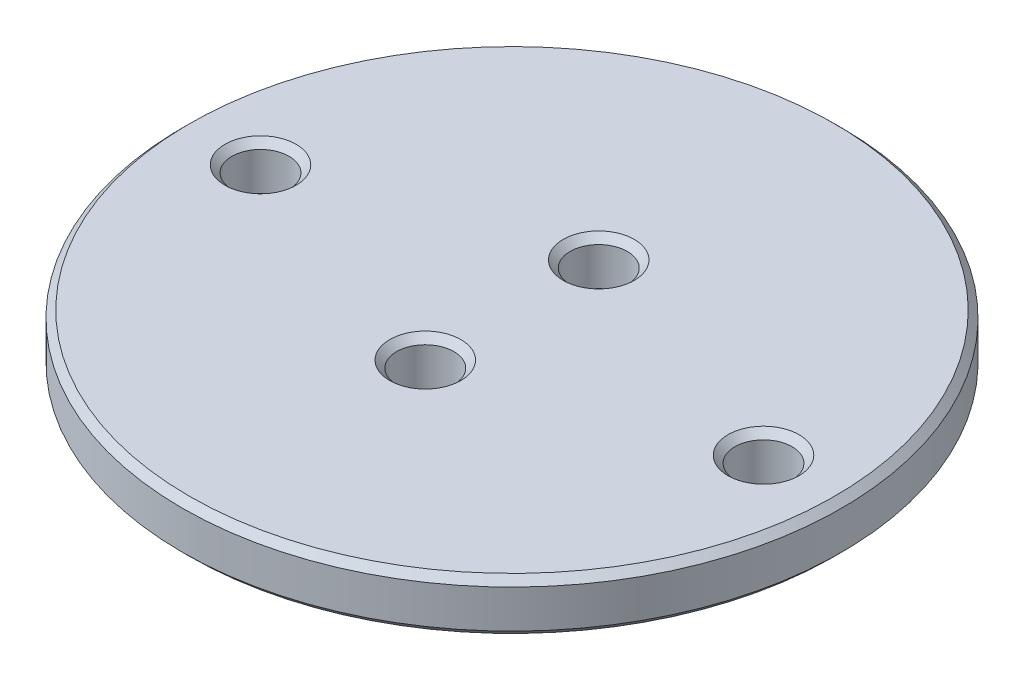
SolidWorks part; units mm, degrees
material "Pine"
ref_plane "Front Plane" through (0, 0, 0) normal (0, 0, 1) x (1, 0, 0)
ref_plane "Top Plane" through (0, 0, 0) normal (0, 1, 0) x (1, 0, 0)
ref_plane "Right Plane" through (0, 0, 0) normal (1, 0, 0) x (0, 0, -1)
sketch "Sketch1" plane through (0, 0, 0) normal (0, 1, 0) x (1, 0, 0)
  line L0 (14.5, 0) -> (-14.5, 0) construction
  line L1 (0, 5) -> (0, -5) construction
  circle A0 centre (0, 0) radius 19
  circle A1 centre (-14.5, 0) radius 1.65
  circle A2 centre (14.5, 0) radius 1.65
  circle A3 centre (0, 5) radius 1.65
  circle A4 centre (0, -5) radius 1.65
  point P7 (0, 0)
  point P12 (0, 0)
  dimension "D1" = 38
  dimension "D2" = 3.3
  dimension "D3" = 29
  dimension "D4" = 10
extrude "Boss-Extrude1" add sketch "Sketch1" along normal blind 3
chamfer "Chamfer1" distance 0.4 angle 45 10 edges at (0, 0, 6.65) (0, 0, -3.35) (14.5, 0, 1.65) (-14.5, 0, 1.65) (0, 0, 19) (0, 3, 6.65) (14.5, 3, 1.65) (0, 3, 19) (-14.5, 3, 1.65) (0, 3, -3.35)
